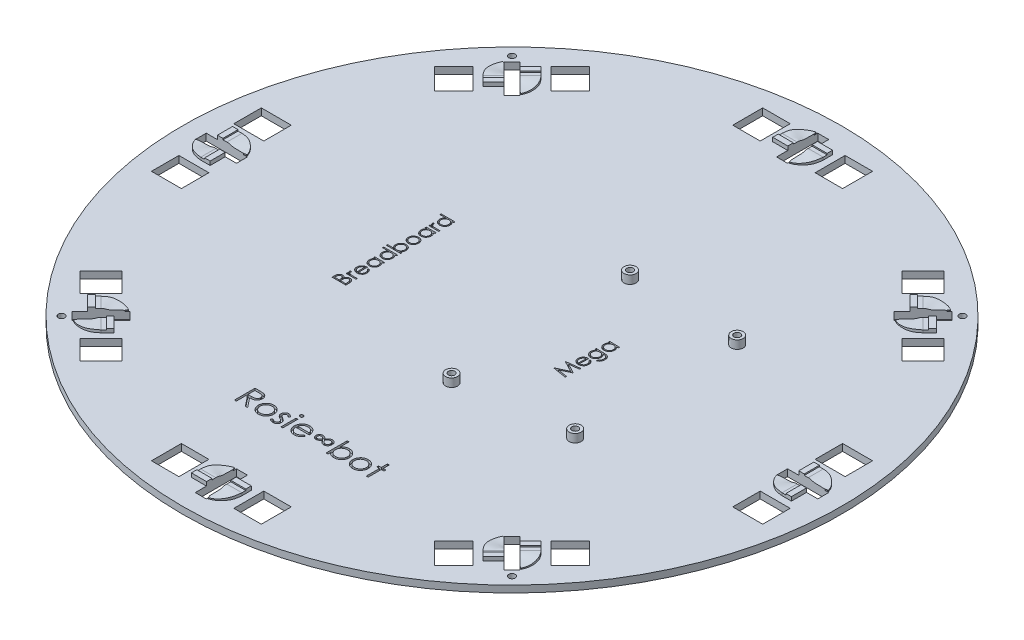
SolidWorks part; units mm, degrees
ref_plane "Front" through (0, 0, 0) normal (0, 0, 1) x (1, 0, 0)
ref_plane "Top" through (0, 0, 0) normal (0, 1, 0) x (1, 0, 0)
ref_plane "Right" through (0, 0, 0) normal (1, 0, 0) x (0, 0, -1)
sketch "Sketch1" plane through (0, 0, 0) normal (0, 1, 0) x (1, 0, 0)
  circle A0 centre (0, 0) radius 152.4
  dimension "D1" = 304.8
extrude "Boss-Extrude1" add sketch "Sketch1" along normal blind 3.175 contours A0
sketch "Sketch2" plane through (0, 3.175, 0) normal (0, 1, 0) x (1, 0, 0)
  line L1 (-2.54, -143.9333) -> (2.54, -143.9333)
  line L2 (-2.54, -143.9333) -> (-2.54, -124.8833)
  line L3 (-2.54, -124.8833) -> (2.54, -124.8833)
  line L4 (2.54, -143.9333) -> (2.54, -124.8833)
  circle A0 centre (0, 0) radius 152.4 construction
  point P4 (0, -124.8833)
  dimension "D1" = 5.08
  dimension "D2" = 19.05
  dimension "D3" = 143.9333
extrude "Cut-Extrude1" cut sketch "Sketch2" against normal up to next and the other way through all contours L1 L4 L3 L2
sketch "Sketch4" plane through (0, 3.175, 0) normal (0, 1, 0) x (1, 0, 0)
  line L0 (0, -134.4083) -> (-2.9434, -125.3495) construction
  line L1 (-2.9434, -125.3495) -> (0, -134.4083) construction
  line L2 (0, -134.4083) -> (-5.5987, -126.7024) construction
  line L3 (0, -134.4083) -> (-7.7059, -128.8097) construction
  line L4 (0, -134.4083) -> (-9.0588, -131.4649) construction
  line L5 (0, -134.4083) -> (-9.525, -134.4083) construction
  line L9 (2.54, -124.8833) -> (-2.54, -124.8833) construction
  line L10 (2.54, -124.8833) -> (2.54, -143.9333) construction
  line L11 (-2.54, -124.8833) -> (-2.54, -143.9333) construction
  line L12 (2.54, -143.9333) -> (-2.54, -143.9333) construction
  circle A0 centre (0, -134.4083) radius 9.525 construction
  point P16 (0, -124.8833)
  point P19 (2.54, -134.4083)
  dimension "D1" = 18
  dimension "D2" = 18
  dimension "D3" = 18
  dimension "D4" = 18
  dimension "D5" = 18
ref_plane "Plane1" through (-39.5016, 0, 12.8349) normal (0.9511, 0, -0.309) x (-0.309, 0, -0.9511)
ref_plane "Plane2" through (-63.915, 0, 46.4369) normal (0.809, 0, -0.5878) x (-0.5878, 0, -0.809)
ref_plane "Plane3" through (-63.915, 0, 87.9714) normal (0.5878, 0, -0.809) x (-0.809, 0, -0.5878)
ref_plane "Plane4" through (-39.5016, 0, 121.5735) normal (0.309, 0, -0.9511) x (-0.9511, 0, -0.309)
ref_plane "Plane5" through (0, 0, 134.4083) normal (0, 0, -1) x (-1, 0, 0)
sketch "Sketch5" plane through (-39.5016, 0, 12.8349) normal (0.9511, 0, -0.309) x (-0.309, 0, -0.9511)
  line L0 (-117.9862, 3.175) -> (-136.1038, 3.175) construction
  line L1 (-119.6103, 3.175) -> (-118.3049, 3.175)
  line L2 (-119.6103, 3.175) -> (-119.6103, 3.683)
  line L3 (-119.6103, 3.683) -> (-118.3049, 3.683)
  line L4 (-118.3049, 3.175) -> (-118.3049, 3.683)
  dimension "D2" = 0.508
sketch "Sketch6" plane through (-63.915, 0, 46.4369) normal (0.809, 0, -0.5878) x (-0.5878, 0, -0.809)
  line L0 (-99.5398, 3.175) -> (-114.9515, 3.175) construction
  line L1 (-104.4173, 3.175) -> (-99.2136, 3.175)
  line L2 (-104.4173, 3.175) -> (-104.4173, 3.775)
  line L3 (-104.4173, 3.775) -> (-99.2136, 3.775)
  line L4 (-99.2136, 3.175) -> (-99.2136, 3.775)
  dimension "D2" = 0.6
sketch "Sketch7" plane through (-63.915, 0, 87.9714) normal (0.5878, 0, -0.809) x (-0.809, 0, -0.5878)
  line L0 (-71.3497, 3.175) -> (-82.547, 3.175) construction
  line L1 (-75.8636, 3.175) -> (-69.4782, 3.175)
  line L2 (-75.8636, 3.175) -> (-75.8636, 4.075)
  line L3 (-75.8636, 4.075) -> (-69.4782, 4.075)
  line L4 (-69.4782, 3.175) -> (-69.4782, 4.075)
  dimension "D2" = 0.9
sketch "Sketch10" plane through (-39.5016, 0, 121.5735) normal (0.309, 0, -0.9511) x (-0.9511, 0, -0.309)
  line L0 (-41.5345, 3.175) -> (-32.4756, 3.175) construction
  line L1 (-38.8637, 3.175) -> (-32.0095, 3.175)
  line L2 (-38.8637, 3.175) -> (-38.8637, 4.375)
  line L3 (-38.8637, 4.375) -> (-32.0095, 4.375)
  line L4 (-32.0095, 3.175) -> (-32.0095, 4.375)
  dimension "D3" = 1.2
sketch "Sketch11" plane through (0, 0, 134.4083) normal (0, 0, -1) x (-1, 0, 0)
  line L0 (0, 3.175) -> (9.525, 3.175) construction
  line L1 (2.54, 3.175) -> (9.525, 3.175)
  line L2 (2.54, 3.175) -> (2.54, 4.375)
  line L3 (2.54, 4.375) -> (9.525, 4.375)
  line L4 (9.525, 3.175) -> (9.525, 4.375)
  dimension "D3" = 1.2
loft "Loft1" add profiles "Sketch5", "Sketch6", "Sketch7", "Sketch10", "Sketch11" connector at (-2.54, 3.683, 126.591) connector at (-2.54, 3.775, 130.9123) connector at (-2.54, 4.075, 132.5629) connector at (-2.54, 4.375, 133.583) connector at (-2.54, 4.375, 134.4083)
sketch "Sketch13" plane through (-104.9799, 0, 134.4083) normal (0, 0, -1) x (-1, 0, 0)
  line L6 (-95.4549, 3.175) -> (-102.4399, 3.175)
  line L7 (-95.4549, 3.175) -> (-95.4549, 4.375)
  line L8 (-95.4549, 4.375) -> (-102.4399, 4.375)
  line L9 (-102.4399, 3.175) -> (-102.4399, 4.375)
extrude "Boss-Extrude4" add sketch "Sketch13" against normal blind 1.7907
sketch "Sketch25" plane through (0, 0, 136.199) normal (0, 0, 1) x (1, 0, 0)
  line L0 (-9.525, 4.375) -> (-2.54, 4.375) construction
  line L1 (-9.525, 3.175) -> (-2.54, 3.175)
  line L2 (-9.525, 3.175) -> (-9.525, 4.975)
  line L3 (-9.525, 4.975) -> (-2.54, 4.975)
  line L4 (-2.54, 3.175) -> (-2.54, 4.975)
  dimension "D1" = 0.6
extrude "Boss-Extrude5" add sketch "Sketch25" along normal blind 2.54
sketch "Sketch14" plane through (-2.54, 0, 0) normal (1, 0, 0) x (0, 0, -1)
  line L0 (-134.4083, 3.175) -> (-134.4083, 0) construction
  line L1 (-124.8833, 0) -> (-143.9333, 0) construction
ref_plane "Plane6" through (0, 0, 0) normal (1, 0, 0) x (0, 0, -1)
sketch "Sketch15" plane through (0, 0, 0) normal (1, 0, 0) x (0, 0, -1)
  line L0 (-134.4083, 0) -> (-134.4083, 3.175) construction
pattern_circular "CirPattern1" count 2 over 360 about axis through (0, 0, 134.4083) along (0, 1, 0) of "Loft1", "Boss-Extrude5", "Boss-Extrude4" reverse direction yes
ref_axis "Axis1" through (0, 50, 0) along (0, -1, 0)
pattern_circular "CirPattern5" count 8 over 360 about axis through (0, 50, 0) along (0, -1, 0) of "CirPattern1", "Cut-Extrude1"
sketch "Sketch18" plane through (0, 3.175, 0) normal (0, 1, 0) x (1, 0, 0)
  line L0 (12.7, 40.64) -> (63.5, 40.64) construction
  line L1 (12.7, 40.64) -> (12.7, -40.64) construction
  line L2 (63.5, -34.29) -> (12.7, -34.29) construction
  line L3 (63.5, -34.29) -> (63.5, 40.64) construction
  line L4 (0, -152.4) -> (0, 152.4) construction
  line L5 (0, -1.7463) -> (0, 1.7463) construction
  line L6 (-152.4, 0) -> (152.4, 0) construction
  line L7 (12.7, 41.91) -> (12.7, 40.64) construction
  circle A0 centre (12.7, 41.91) radius 2.77
  circle A1 centre (12.7, -40.64) radius 2.77
  circle A2 centre (63.5, -34.29) radius 2.77
  circle A3 centre (63.5, 40.64) radius 2.77
  circle A4 centre (12.7, -40.64) radius 1.5
  circle A5 centre (12.7, 41.91) radius 1.5
  circle A6 centre (63.5, 40.64) radius 1.5
  circle A7 centre (63.5, -34.29) radius 1.5
  circle A8 centre (0, 0) radius 152.4 construction
  point P13 (0, 0)
  point P22 (12.7, 0)
  point P23 (0, 0)
  point P24 (23.2549, -34.29)
  point P26 (12.7, -34.29)
  dimension "D7" = 12.7
  dimension "D5" = 3
  dimension "D6" = 1.27
  dimension "D1" = 82.55
  dimension "D2" = 74.93
  dimension "D3" = 50.8
  dimension "D4" = 1.27
sketch "Sketch19" plane through (0, 3.175, 0) normal (0, 1, 0) x (1, 0, 0)
  line L0 (-104.171, -104.171) -> (0, 0) construction
  line L1 (0, -152.4) -> (0, 152.4) construction
  circle A1 centre (-104.171, -104.171) radius 1.5
  circle A4 centre (0, 0) radius 152.4 construction
  dimension "D4" = 3
  dimension "D6" = 147.32
  dimension "D5" = 45
extrude "Cut-Extrude2" cut sketch "Sketch19" against normal through all
pattern_circular "CirPattern7" count 4 over 360 about axis through (0, 50, 0) along (0, -1, 0) of "Cut-Extrude2"
extrude "Boss-Extrude3" add sketch "Sketch18" along normal blind 3.81
sketch "Sketch23" plane through (0, 3.175, 0) normal (0, 1, 0) x (1, 0, 0)
  line L9 (-2.54, -138.739) -> (-2.54, -143.9333) construction
  line L10 (-25.4, -127.4805) -> (-12.7, -127.4805)
  line L11 (-25.4, -127.4805) -> (-25.4, -141.3362)
  line L16 (-25.4, -141.3362) -> (-12.7, -141.3362)
  line L17 (-12.7, -127.4805) -> (-12.7, -141.3362)
  line L19 (2.54, -124.8833) -> (2.54, -130.0776) construction
  line L20 (0, -50) -> (0, 50) construction
  line L21 (12.7, -127.4805) -> (12.7, -141.3362)
  line L22 (25.4, -141.3362) -> (12.7, -141.3362)
  line L23 (25.4, -127.4805) -> (25.4, -141.3362)
  line L24 (25.4, -127.4805) -> (12.7, -127.4805)
  point P8 (-2.54, -141.3362)
  point P9 (2.54, -127.4805)
  dimension "D1" = 12.7
  dimension "D2" = 10.16
extrude "Cut-Extrude6" cut sketch "Sketch23" against normal through all
sketch "Sketch17" plane through (0, 3.175, 0) normal (0, 1, 0) x (1, 0, 0)
  line L0 (-31.75, -97.8162) -> (31.75, -97.8162) construction
  point P3 (0, -97.8162)
  dimension "D2" = 97.8162
  dimension "D1" = 63.5
pattern_circular "CirPattern8" count 8 over 360 about axis through (0, 50, 0) along (0, -1, 0) of "Cut-Extrude6"
sketch "Sketch16" plane through (0, 3.175, 0) normal (0, 1, 0) x (1, 0, 0)
  line L0 (-31.75, -97.8162) -> (31.75, -97.8162) construction
  text T0 "Rosie∞bot\r\n" font "Century Gothic" height in points 36
extrude "Cut-Extrude4" cut sketch "Sketch16" against normal blind 1.27
sketch "Sketch22" plane through (0, 3.175, 0) normal (0, 1, 0) x (1, 0, 0)
  line L0 (-50.8, 25.1735) -> (-50.8, -31.2294) construction
  text T0 "Breadboard"
  dimension "D1" = 50.8
extrude "Cut-Extrude5" cut sketch "Sketch22" against normal blind 1.27
sketch "Sketch24" plane through (0, 3.175, 0) normal (0, 1, 0) x (1, 0, 0)
  line L0 (36.7515, -12.6663) -> (37.3848, 12.6663) construction
  circle A0 centre (12.7, 41.91) radius 1.5 construction
  circle A1 centre (63.5, 40.64) radius 1.5 construction
  text T0 "Mega"
  point P12 (37.0681, 0)
extrude "Cut-Extrude7" cut sketch "Sketch24" against normal blind 1.27
